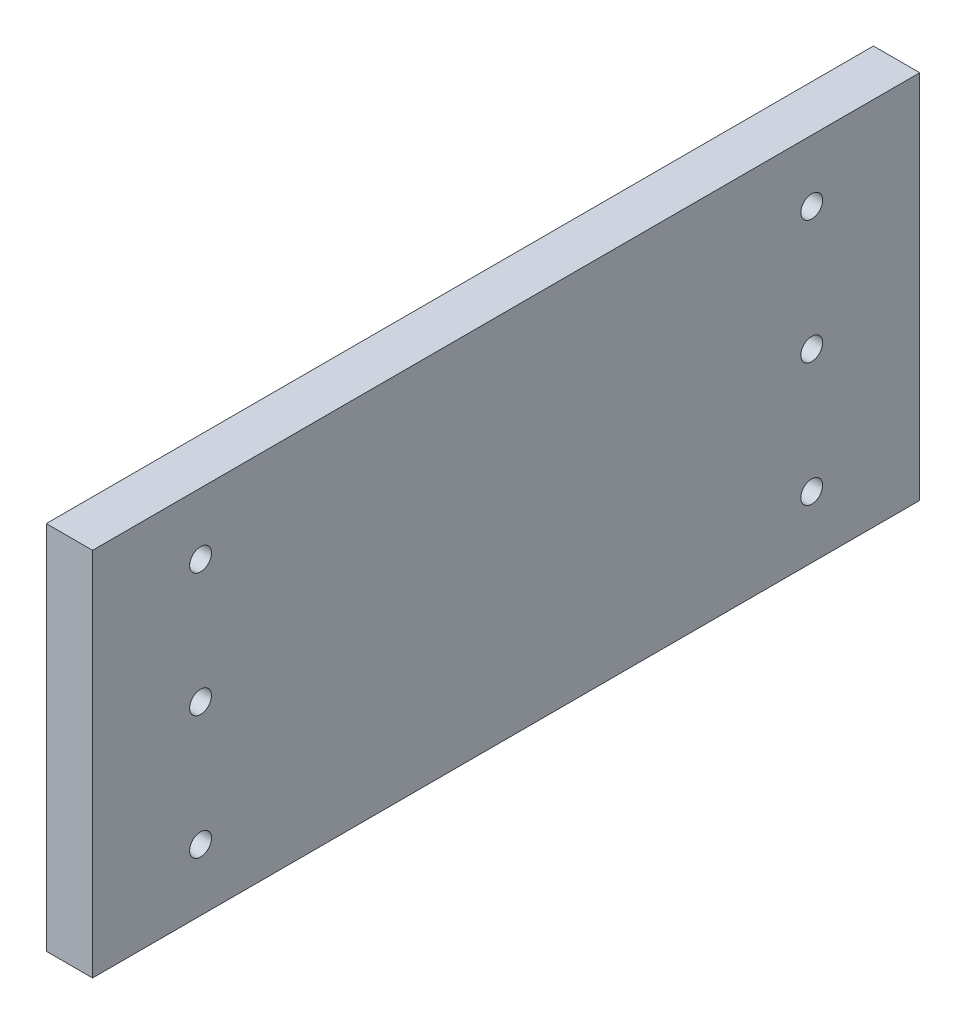
SolidWorks part; units mm, degrees
material "Plain Carbon Steel"
ref_plane "Front Plane" through (0, 0, 0) normal (0, 0, 1) x (1, 0, 0)
ref_plane "Top Plane" through (0, 0, 0) normal (0, 1, 0) x (1, 0, 0)
ref_plane "Right Plane" through (0, 0, 0) normal (1, 0, 0) x (0, 0, -1)
sketch "Sketch1" plane through (0, 0, 0) normal (0, 0, 1) x (1, 0, 0)
  line L1 (-4.7625, 38.1) -> (4.7625, 38.1)
  line L2 (-4.7625, 38.1) -> (-4.7625, -38.1)
  line L3 (-4.7625, -38.1) -> (4.7625, -38.1)
  line L4 (4.7625, 38.1) -> (4.7625, -38.1)
  line L5 (-4.7625, 38.1) -> (4.7625, -38.1) construction
  line L6 (-4.7625, -38.1) -> (4.7625, 38.1) construction
  point P0 (0, 0)
  dimension "D1" = 9.525
  dimension "D2" = 76.2
extrude "Boss-Extrude1" add sketch "Sketch1" along normal blind 170.18
hole_wizard "#8 Clearance Hole1" positions "Sketch3" profile "Sketch2" hole size "#8" standard "ANSI Inch" end condition through all
sketch "Sketch3" plane through (4.7625, 0, 0) normal (1, 0, 0) x (0, 0, -1)
  line L0 (-170.18, -38.1) -> (0, -38.1) construction
  line L1 (-170.18, -38.1) -> (-170.18, 38.1) construction
  line L2 (0, -38.1) -> (0, 38.1) construction
  point P0 (-147.955, 25.4)
  point P2 (-147.955, 0)
  point P4 (-147.955, -25.4)
  point P6 (-22.225, 25.4)
  point P8 (-22.225, 0)
  point P10 (-22.225, -25.4)
  point P17 (-170.18, 0)
  dimension "D1" = 25.4
  dimension "D2" = 25.4
  dimension "D3" = 12.7
  dimension "D4" = 22.225
  dimension "D5" = 22.225
sketch "Sketch2" plane through (4.7625, 25.4, 147.955) normal (0, 1, 0) x (0, 0, -1)
  line L0 (0, 0) -> (0, 9.525)
  line L1 (0, 9.525) -> (2.2479, 9.525)
  line L2 (2.2479, 9.525) -> (2.2479, 0)
  line L5 (2.2479, 0) -> (0, 0)
  line L11 (0, -6.35) -> (0, 107.95) construction
  dimension "Thru Hole Dia." = 4.4958
  dimension "Thru Hole Depth" = 9.525
